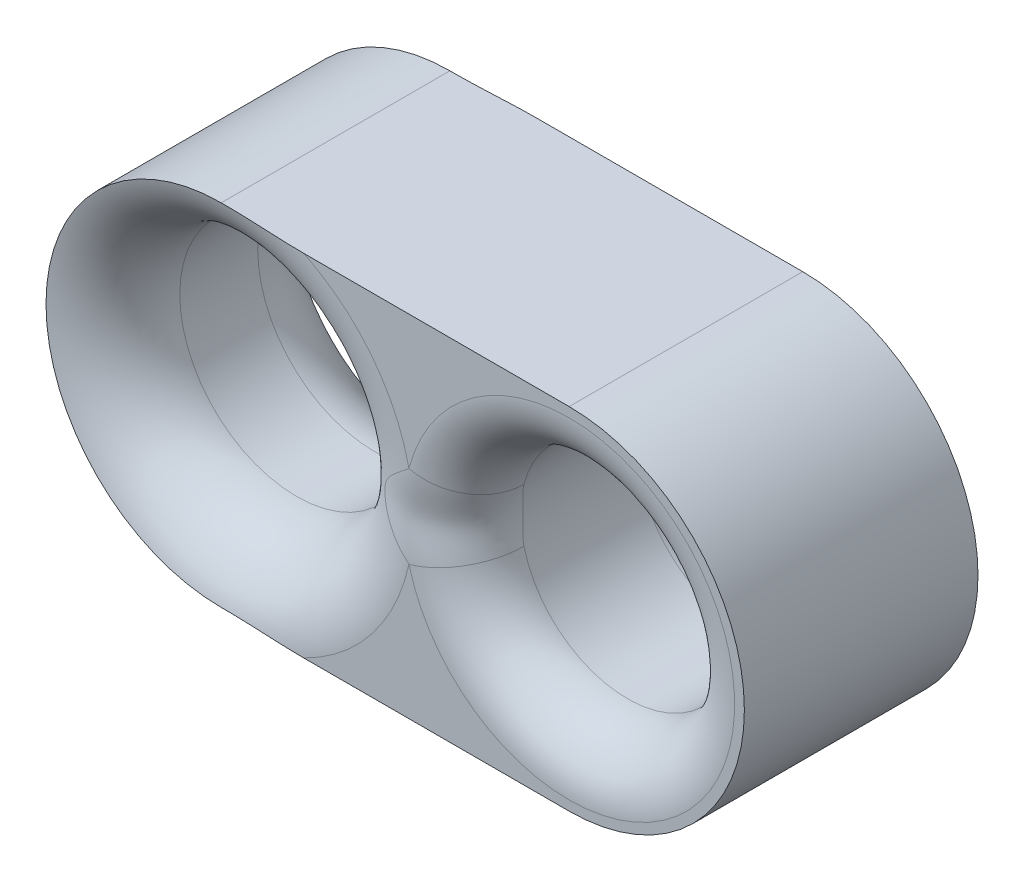
SolidWorks part; units mm, degrees
ref_plane "Alzado" through (0, 0, 0) normal (0, 0, 1) x (1, 0, 0)
ref_plane "Planta" through (0, 0, 0) normal (0, 1, 0) x (1, 0, 0)
ref_plane "Vista lateral" through (0, 0, 0) normal (1, 0, 0) x (0, 0, -1)
sketch "Croquis2" plane through (0, 0, 0) normal (0, 0, 1) x (1, 0, 0)
  line L0 (-22.555, 0) -> (30.0977, 0) construction
  line L1 (0, 9.13) -> (0, -9.4871) construction
  line L2 (-3, 7.7177) -> (-3, -10.2997) construction
  line L3 (-9, 0) -> (9, 0) construction
  line L4 (-9, 9) -> (9, 9)
  line L5 (-9, -9) -> (9, -9)
  circle A0 centre (9, 0) radius 5.5
  circle A1 centre (-9, 0) radius 6
  arc A2 (-9, 9) -> (-9, -9) centre (-9, 0) ccw
  arc A3 (9, -9) -> (9, 9) centre (9, 0) ccw
  point P11 (0, 0)
  dimension "D1" = 12
  dimension "D2" = 11
  dimension "D5" = 9
  dimension "D3" = 9
  dimension "D4" = 3
extrude "Saliente-Extruir1" add sketch "Croquis2" along normal mid plane 12
fillet "Redondeo1" radius 4 2 edges at (-3, 0, 6) (-3, 0, -6)
fillet "Redondeo2" radius 3 2 edges at (14.5, 0, -6) (14.5, 0, 6)
sketch "Croquis4" plane through (0, 0, 0) normal (0, 1, 0) x (1, 0, 0)
  line L0 (18, 6) -> (9, 6) construction
  line L2 (9, -6) -> (18, -6) construction
  line L3 (-4.6411, 6) -> (9, 6) construction
  line L4 (9, -6) -> (-4.6411, -6) construction
  line L6 (-9, 5.873) -> (-18, 5.873) construction
  line L7 (-18, -5.873) -> (-9, -5.873) construction
  line L8 (18, 6) -> (9, 6)
  line L10 (9, -6) -> (18, -6)
  line L11 (-4.6411, 6) -> (9, 6)
  line L12 (9, -6) -> (-4.6411, -6)
  line L14 (-9, 5.873) -> (-18, 5.873)
  line L15 (-18, -5.873) -> (-9, -5.873)
  line L16 (-18, -4.873) -> (18, -6)
  line L17 (-18, 5.873) -> (-18, -5.873) construction
  line L18 (-18, -5.873) -> (-18, -4.873)
  line L20 (-18, 5.873) -> (18, 5)
  line L21 (18, 5) -> (18, 6)
  spline S0 degree 3 poles (-210.1396, 2997.7872) (-84.6689, 20.461) (-45.483, 4.2183) (23.4985, 7.2741) (53.5798, 16.7723) (171.4929, -2987.9044) knots -26.121204 -26.121204 -26.121204 -26.121204 0.5 0.5 21.376103 21.376103 21.376103 21.376103 only from (-9, 5.873) to (-4.6411, 6) construction
  spline S1 degree 3 poles (171.4989, 2988.0555) (53.5808, -16.7726) (23.499, -7.2741) (-45.4829, -4.2183) (-84.6686, -20.4609) (-210.1384, -2997.7584) knots -20.376453 -20.376453 -20.376453 -20.376453 0.5 0.5 27.121118 27.121118 27.121118 27.121118 only from (-4.6411, -6) to (-9, -5.873) construction
  spline S2 degree 3 poles (-9, 5.873) (-8.2729, 5.873) (-7.5466, 5.8988) (-6.0942, 5.9632) (-5.3682, 6) (-4.6411, 6) knots 0 0 0 0 0.5 0.5 1 1 1 1
  spline S3 degree 3 poles (-4.6411, -6) (-5.3682, -6) (-6.0942, -5.9632) (-7.5466, -5.8988) (-8.2729, -5.873) (-9, -5.873) knots 0 0 0 0 0.5 0.5 1 1 1 1
  dimension "D1" = 1
  dimension "D2" = 1
